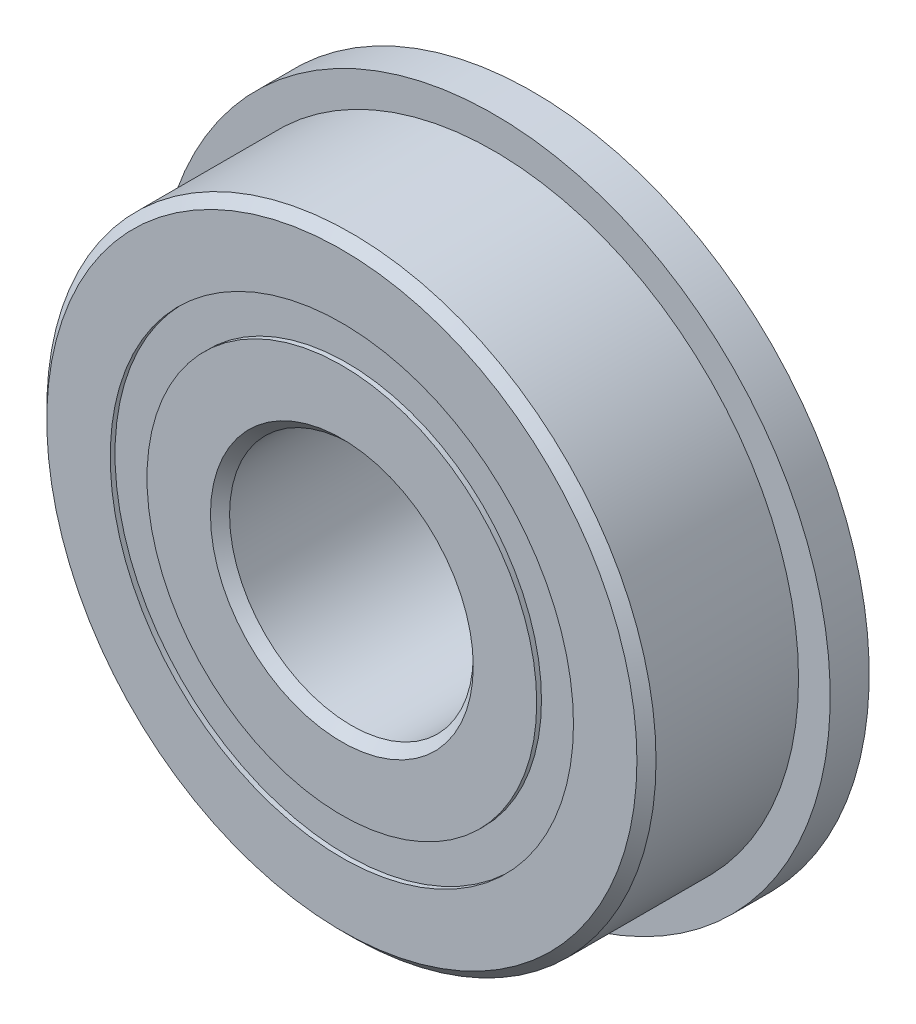
SolidWorks part; units mm, degrees
material "Stainless Steel (ferritic)"
ref_plane "Front Plane" through (0, 0, 0) normal (0, 0, 1) x (1, 0, 0)
ref_plane "Top Plane" through (0, 0, 0) normal (0, 1, 0) x (1, 0, 0)
ref_plane "Right Plane" through (0, 0, 0) normal (1, 0, 0) x (0, 0, -1)
sketch "Sketch1" plane through (0, 0, 0) normal (1, 0, 0) x (0, 0, -1)
  line L0 (-2.4892, 0) -> (2.4892, 0) construction
  line L1 (0, 7.9375) -> (0, -7.9375) construction
  line L2 (2.4892, 7.9375) -> (-2.4892, 7.9375) construction
  line L9 (0, 7.9375) -> (0, 5.5563) construction
  line L10 (0, 5.5563) -> (0, 3.175) construction
  point P14 (0, 3.175)
  dimension "Width" = 4.9784
  dimension "OD" = 15.875
  dimension "Shaft Dia" = 6.35
sketch "Sketch2" plane through (0, 0, 0) normal (1, 0, 0) x (0, 0, -1)
  line L0 (1.9844, 0) -> (-1.9844, 0) construction
  line L1 (2.4892, 6.0352) -> (1.4732, 6.0352) construction
  line L2 (2.4892, 6.0352) -> (2.4892, 8.763) construction
  line L3 (2.4892, 8.763) -> (1.4732, 8.763) construction
  line L4 (1.4732, 6.0352) -> (1.4732, 8.763) construction
  dimension "Th" = 1.016
  dimension "Flange OD" = 17.526
  dimension "D1" = 0.479
sketch "Sketch" plane through (0, 0, 0) normal (1, 0, 0) x (0, 0, -1)
  line L0 (-2.4892, 0) -> (2.4892, 0) construction
  line L1 (0, 7.9375) -> (0, -7.9375) construction
  line L2 (2.2403, 7.9375) -> (-2.2403, 7.9375)
  line L3 (-2.2403, 7.9375) -> (-2.4892, 7.6886)
  line L4 (-2.4892, 7.6886) -> (-2.4892, 6.0352)
  line L5 (-2.4892, 6.0352) -> (-1.1063, 6.0352)
  line L6 (2.4892, 6.0352) -> (1.1063, 6.0352)
  line L7 (2.4892, 7.6886) -> (2.4892, 6.0352)
  line L8 (2.2403, 7.9375) -> (2.4892, 7.6886)
  line L9 (0, 7.9375) -> (0, 5.5563) construction
  line L10 (0, 5.5563) -> (0, 3.175) construction
  arc A0 (-1.1063, 6.0352) -> (1.1063, 6.0352) centre (0, 5.5563) cw
  point P14 (0, 3.175)
  dimension "D1" = 45
  dimension "D2" = 0.2489
  dimension "D3" = 2.2126
  dimension "D4" = 0.479
revolve "Revolve1" add sketch "Sketch" angle 360 about L0
sketch "Sketch3" plane through (0, 0, 0) normal (1, 0, 0) x (0, 0, -1)
  line L0 (-2.4892, 5.0773) -> (-1.1063, 5.0773)
  line L1 (0, 7.9375) -> (0, -7.9375) construction
  line L2 (-2.4892, 7.6886) -> (-2.4892, 6.0352) construction
  line L3 (-2.4892, 5.0773) -> (-2.4892, 3.4239)
  line L4 (-2.2403, 7.9375) -> (-2.4892, 7.6886) construction
  line L5 (-2.4892, 3.4239) -> (-2.2403, 3.175)
  line L6 (-2.2403, 3.175) -> (2.2403, 3.175)
  line L7 (2.2403, 7.9375) -> (2.2403, -7.9375) construction
  line L8 (2.2403, 3.175) -> (2.4892, 3.4239)
  line L9 (2.4892, -7.6886) -> (2.4892, 7.6886) construction
  line L10 (2.4892, 3.4239) -> (2.4892, 5.0773)
  line L11 (2.4892, 5.0773) -> (1.1063, 5.0773)
  line L13 (2.2403, 7.9375) -> (2.4892, 7.6886) construction
  arc A0 (1.1063, 6.0352) -> (-1.1063, 6.0352) centre (0, 5.5563) ccw construction
  arc A1 (1.1063, 5.0773) -> (-1.1063, 5.0773) centre (0, 5.5562) cw
revolve "Revolve3" add sketch "Sketch3" angle 360 about L0
sketch "Sketch4" plane through (0, 0, 0) normal (1, 0, 0) x (0, 0, -1)
  line L0 (-1.2055, 5.5563) -> (1.2055, 5.5563)
  arc A2 (-1.2055, 5.5563) -> (1.2055, 5.5563) centre (0, 5.5563) cw
  arc A3 (1.1063, 6.0352) -> (-1.1063, 6.0352) centre (0, 5.5563) ccw construction
revolve "Revolve4" add sketch "Sketch4" angle 360 about L0
ref_axis "Axis1" through (0, 0, -2.4892) along (0, 0, 1)
pattern_circular "CirPattern1" count 14 every 25.714 about axis through (0, 0, -2.4892) along (0, 0, 1) of bodies 104
sketch "Sketch5" plane through (0, 0, 0) normal (1, 0, 0) x (0, 0, -1)
  line L0 (-2.4892, 6.0352) -> (-1.1063, 6.0352) construction
  line L1 (-2.3647, 6.0352) -> (-1.2055, 6.0352)
  line L2 (-2.3647, 6.0352) -> (-2.3647, 5.0773)
  line L3 (-2.3647, 5.0773) -> (-1.2055, 5.0773)
  line L4 (-1.2055, 6.0352) -> (-1.2055, 5.0773)
  line L5 (-2.4892, 5.0773) -> (-1.1063, 5.0773) construction
  line L6 (2.4892, 6.0352) -> (1.1063, 6.0352) construction
  line L7 (2.3647, 6.0352) -> (1.2055, 6.0352)
  line L8 (2.3647, 6.0352) -> (2.3647, 5.0773)
  line L9 (2.3647, 5.0773) -> (1.2055, 5.0773)
  line L10 (1.2055, 6.0352) -> (1.2055, 5.0773)
  line L11 (2.4892, 5.0773) -> (1.1063, 5.0773) construction
  line L12 (-2.2403, 7.9375) -> (-2.4892, 7.6886) construction
  point P18 (-2.3647, 7.813)
revolve "Revolve5" add sketch "Sketch5" angle 360 about L0
sketch "Sketch6" plane through (0, 0, 0) normal (1, 0, 0) x (0, 0, -1)
  line L0 (2.4892, 0) -> (-2.4892, 0) construction
  line L1 (2.4892, 6.0352) -> (1.4732, 6.0352)
  line L2 (2.4892, 6.0352) -> (2.4892, 8.763)
  line L3 (2.4892, 8.763) -> (1.4732, 8.763)
  line L4 (1.4732, 6.0352) -> (1.4732, 8.763)
  dimension "Th" = 1.016
  dimension "Flange OD" = 17.526
revolve "Revolve6" add sketch "Sketch6" angle 360 about L0
sketch "Sketch7" plane through (0, 0, 0) normal (1, 0, 0) x (0, 0, -1)
  line L1 (2.4892, 7.9375) -> (-2.4892, 7.9375) construction
  line L2 (2.4892, 7.9375) -> (-2.4892, 7.9375) construction
  line L3 (2.4892, -7.9375) -> (-2.4892, -7.9375) construction
  line L4 (2.4892, -8.763) -> (2.4892, 8.763) construction
  line L5 (2.4892, 7.9375) -> (2.4892, 8.763) construction
  line L6 (2.4892, 8.763) -> (1.4732, 8.763) construction
  dimension "D1" = 15.875
  dimension "D2" = 4.9784
sketch "Sketch8" plane through (0, 0, 0) normal (0, 0, 1) x (1, 0, 0)
  circle A0 centre (0, 0) radius 3.175 construction
  dimension "D1" = 6.35
equation "\"D2@Sketch\" = \"Width@Sketch1\" * .05"
equation "\"D3@Sketch\" = \"Width@Sketch1\" / 2.25"
equation "\"D4@Sketch\"=(  (  ( \"OD@Sketch1\" - \"Width@Sketch1\" )  / 2 )  / 3.25 )  / 3.5"
equation "\"D2@CirPattern1\" = 360/\"Balls@CirPattern1\""
equation "\"D1@Sketch2\"=(  (  ( \"OD@Sketch1\" - \"Width@Sketch1\" )  / 2 )  / 3.25 )  / 3.5"
